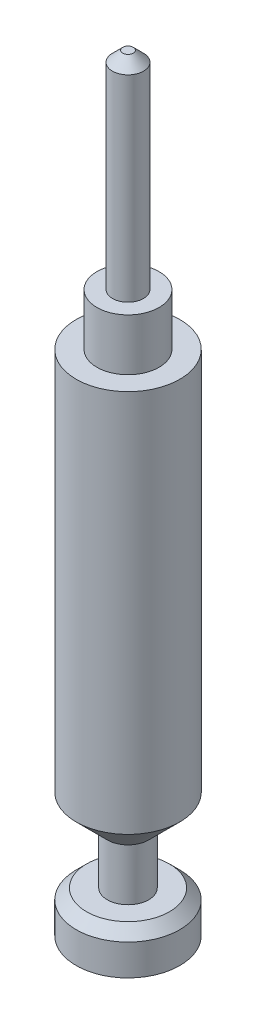
SolidWorks part; units mm, degrees
material "1060 Alloy"
ref_plane "Front Plane" through (0, 0, 0) normal (0, 0, 1) x (1, 0, 0)
ref_plane "Top Plane" through (0, 0, 0) normal (0, 1, 0) x (1, 0, 0)
ref_plane "Right Plane" through (0, 0, 0) normal (1, 0, 0) x (0, 0, -1)
sketch "Sketch1" plane through (0, 0, 0) normal (0, 1, 0) x (1, 0, 0)
  circle A0 centre (0, 0) radius 5
  dimension "D1" = 10
extrude "Boss-Extrude1" add sketch "Sketch1" along normal blind 40
sketch "Sketch2" plane through (0, 40, 0) normal (0, 1, 0) x (1, 0, 0)
  circle A0 centre (0, 0) radius 3
  dimension "D1" = 6
extrude "Boss-Extrude2" add sketch "Sketch2" along normal blind 5
sketch "Sketch3" plane through (0, 45, 0) normal (0, 1, 0) x (1, 0, 0)
  circle A0 centre (0, 0) radius 1.5
  dimension "D1" = 3
extrude "Boss-Extrude3" add sketch "Sketch3" along normal blind 20
chamfer "Chamfer1" distance 1 angle 45 1 edges at (0, 65, 1.5)
sketch "Sketch4" plane through (0, 0, 0) normal (0, -1, 0) x (1, 0, 0)
  circle A0 centre (0, 0) radius 2
  dimension "D1" = 4
extrude "Boss-Extrude4" add sketch "Sketch4" along normal blind 5
sketch "Sketch5" plane through (0, -5, 0) normal (0, -1, 0) x (1, 0, 0)
  circle A0 centre (0, 0) radius 5
  circle A1 centre (0, 0) radius 5 construction
extrude "Boss-Extrude5" add sketch "Sketch5" along normal blind 4
chamfer "Chamfer2" distance 3 angle 45 1 edges at (0, 0, 5)
chamfer "Chamfer3" distance 1 angle 45 1 edges at (0, -5, -5)
